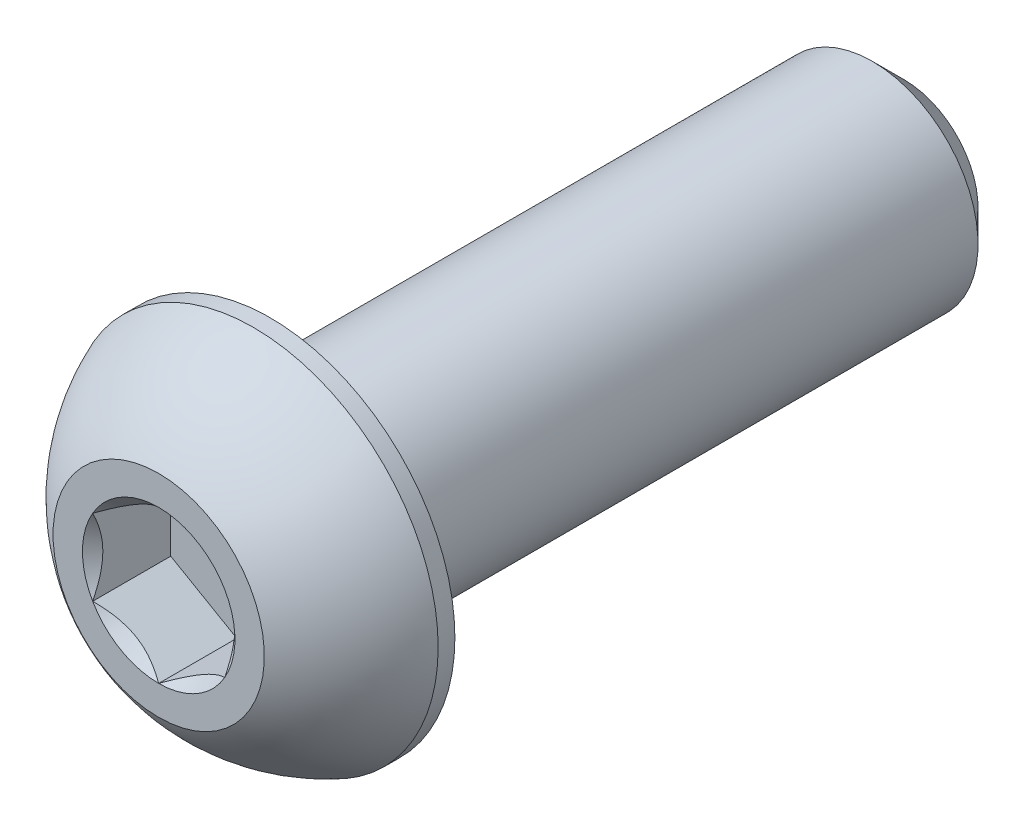
SolidWorks part; units mm, degrees
material "Alloy Steel"
ref_plane "Front" through (0, 0, 0) normal (0, 0, 1) x (1, 0, 0)
ref_plane "Top" through (0, 0, 0) normal (0, 1, 0) x (1, 0, 0)
ref_plane "Right" through (0, 0, 0) normal (1, 0, 0) x (0, 0, -1)
sketch "Sketch1" plane through (0, 0, 0) normal (1, 0, 0) x (0, 0, -1)
  line L2 (3.3528, 3.175) -> (22.4028, 3.175)
  line L3 (22.4028, 3.175) -> (22.4028, 0)
  line L4 (22.4028, 0) -> (3.3528, 0)
  line L6 (2.8499, 5.5499) -> (3.3528, 5.5499) construction
  line L7 (22.4028, 3.175) -> (22.4028, -3.175) construction
  line L8 (0, 0) -> (3.3528, 0) construction
  line L9 (3.3528, 5.5499) -> (3.3528, -5.5499) construction
  line L11 (3.3528, 3.175) -> (3.3528, 0)
  line L13 (0, 1.9844) -> (0, -1.9844) construction
  line L14 (0, 1.9844) -> (0, 3.175) construction
  arc A3 (0, 3.175) -> (2.8499, 5.5499) centre (5.0603, 0) cw construction
  dimension "D1" = 0.5029
revolve "Revolve1" add sketch "Sketch1" angle 360 mid plane about L4
sketch "Sketch3" plane through (0, 0, -22.4028) normal (0, 0, -1) x (-1, 0, 0)
  circle A0 centre (0, 0) radius 3.175
curve "Helix/Spiral1" pitch 1.27 height 20.32 turns 16
sketch "Sketch2" plane through (0, 0, 0) normal (1, 0, 0) x (0, 0, -1)
  line L0 (22.4028, 3.175) -> (23.514, 3.175)
  line L1 (23.514, 3.175) -> (23.0378, 2.3501)
  line L2 (23.0378, 2.3501) -> (22.879, 2.3501)
  line L3 (22.879, 2.3501) -> (22.4028, 3.175)
  line L4 (22.6409, 2.7626) -> (23.2759, 2.7626) construction
  dimension "D1" = 60
  dimension "D2" = 0.1588
  dimension "D3" = 0.635
chamfer "Chamfer1" distance 0.9525 angle 45 1 edges at (0, 3.175, -22.4028)
sweep "Cut-Sweep1" [suppressed] cut profiles "Sketch2" path "Helix/Spiral1"
sketch "Sketch7" plane through (0, 0, 0) normal (1, 0, 0) x (0, 0, -1)
  line L6 (2.8499, 5.5499) -> (3.3528, 5.5499) construction
  line L8 (0, 0) -> (3.3528, 0) construction
  line L11 (3.3528, 5.5499) -> (3.3528, -5.5499) construction
  line L12 (2.8499, 5.5499) -> (3.3528, 5.5499)
  line L13 (0, 0) -> (3.3528, 0)
  line L14 (0, 1.9844) -> (0, -1.9844) construction
  line L15 (3.3528, 5.5499) -> (3.3528, 0)
  line L16 (0, 3.175) -> (0, 0)
  arc A2 (2.8499, 5.5499) -> (0, 3.175) centre (5.0603, 0) ccw construction
  arc A3 (2.8499, 5.5499) -> (0, 3.175) centre (5.0603, 0) ccw
revolve "Revolve2" add sketch "Sketch7" angle 360 mid plane about L13
sketch "Sketch5" plane through (0, 0, 0) normal (0, 0, 1) x (1, 0, 0)
  line L1 (1.9844, -1.1457) -> (1.9844, 1.1457)
  line L2 (1.9844, 1.1457) -> (0, 2.2914)
  line L3 (0, 2.2914) -> (-1.9844, 1.1457)
  line L4 (-1.9844, 1.1457) -> (-1.9844, -1.1457)
  line L5 (-1.9844, -1.1457) -> (0, -2.2914)
  line L6 (0, -2.2914) -> (1.9844, -1.1457)
  circle A0 centre (0, 0) radius 1.9844 construction
extrude "Cut-Extrude2" cut sketch "Sketch5" against normal blind 2.347
sketch "Sketch6" plane through (0, 0, 0) normal (0, 0, 1) x (1, 0, 0)
  circle A0 centre (0, 0) radius 2.2914
extrude "Cut-Extrude3" cut sketch "Sketch6" against normal blind 2.347 draft 45
sketch "Sketch9" [suppressed] plane through (0, 0, -3.3528) normal (0, 0, 1) x (1, 0, 0)
  circle A2 centre (0, 0) radius 3.175
extrude "Boss-Extrude2" [suppressed] add sketch "Sketch9" against normal offset from surface (12.7 mm away) 22.225
sketch "Sketch10" plane through (0, 0, 0) normal (1, 0, 0) x (0, 0, -1)
  line L0 (22.4028, 3.175) -> (22.4028, -3.175) construction
  point P0 (20.4978, -3.175)
  dimension "D1" = 1.905
equation "\"D3@Helix/Spiral1\" = \"Lg@Sketch1\" + \"D4@Helix/Spiral1\""
equation "\"D2@Sketch2\" = \"D4@Helix/Spiral1\" * .125"
equation "\"D3@Sketch2\" = \"D4@Helix/Spiral1\" * .5"
equation "\"D1@Chamfer1\" = \"D4@Helix/Spiral1\" * .75"
equation "\"D1@Cut-Extrude2\" = \"Head Ht@Sketch1\" * .7"
equation "\"D1@Sketch1\" = \"Head Ht@Sketch1\" * .15"
equation "\"D1@Sketch10\" = \"D4@Helix/Spiral1\" * 1.5"
equation "\"D1@Cut-Extrude3\" = \"D1@Cut-Extrude2\""
